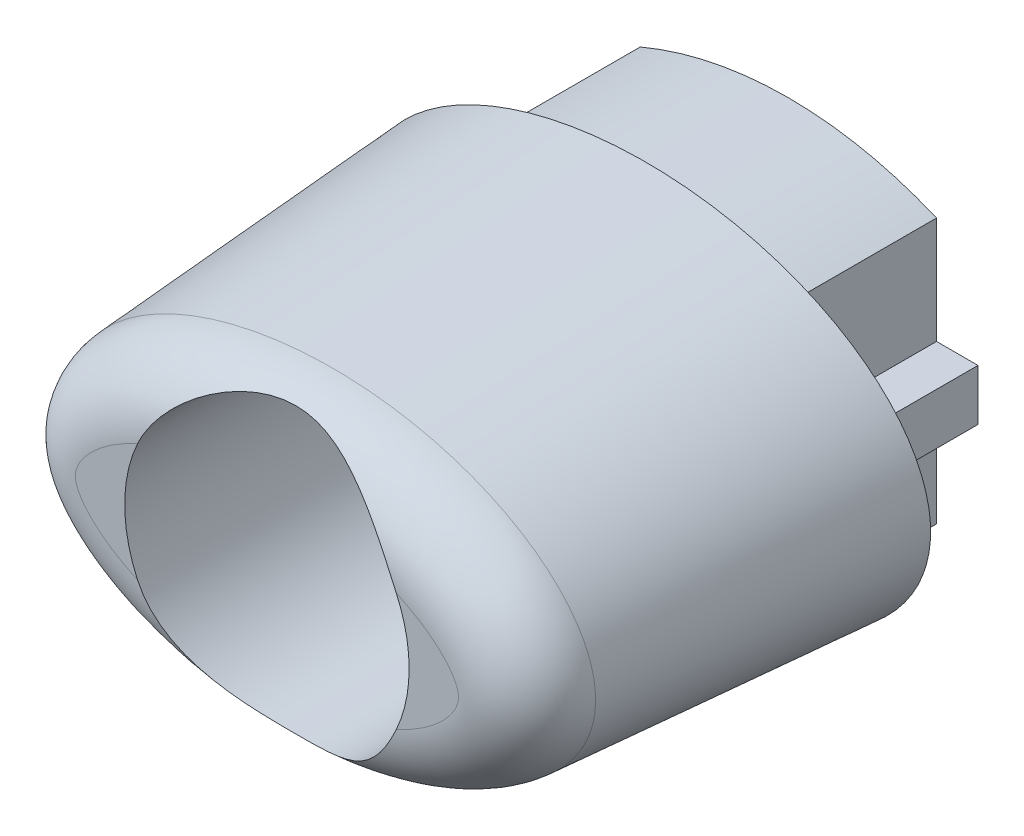
SolidWorks part; units mm, degrees
ref_plane "Front Plane" through (0, 0, 0) normal (0, 0, 1) x (1, 0, 0)
ref_plane "Top Plane" through (0, 0, 0) normal (0, 1, 0) x (1, 0, 0)
ref_plane "Right Plane" through (0, 0, 0) normal (1, 0, 0) x (0, 0, -1)
sketch "Sketch1" plane through (0, 0, 0) normal (0, 0, 1) x (1, 0, 0)
  line L0 (0, -4.2377) -> (0, 4.8119) construction
  line L1 (-6.9182, 0) -> (6.9553, 0) construction
  line L2 (-3.125, -2.7947) -> (-3.125, -0.5398)
  line L30 (-3.125, 0.5398) -> (-3.125, 2.7947)
  line L35 (3.125, 0.5398) -> (3.125, 2.7947)
  line L36 (-4, 0.5398) -> (-3.125, 0.5398)
  line L37 (4, -0.5398) -> (3.125, -0.5398)
  line L38 (4, -0.5398) -> (4, 0.5398)
  line L39 (4, 0.5398) -> (3.125, 0.5398)
  line L42 (-4, -0.5398) -> (-3.125, -0.5398)
  line L43 (-4, -0.5398) -> (-4, 0.5398)
  line L44 (3.125, -0.5398) -> (3.125, -2.7947)
  arc A2 (-3.125, 2.7947) -> (3.125, 2.7947) centre (0, -4.5731) cw
  arc A3 (-3.125, -2.7947) -> (3.125, -2.7947) centre (0, 4.5731) ccw
  ellipse E2 centre (0, 0) end of major axis (-5.39, 0) minor radius 3.43 construction
  dimension "D1" = 8
  dimension "D2" = 6.25
extrude "Boss-Extrude1" add sketch "Sketch1" along normal blind 3
sketch "Sketch3" plane through (0, 0, 3) normal (0, 0, 1) x (1, 0, 0)
  line L0 (0, 3.75) -> (0, -3.75) construction
  line L1 (-6, 0) -> (6, 0) construction
  ellipse E0 centre (0, 0) end of major axis (-6, 0) minor radius 3.75
  dimension "D1" = 7.5
  dimension "D2" = 12
extrude "Boss-Extrude2" add sketch "Sketch3" along normal blind 8 draft 4
sketch "Sketch7" plane through (0, 0, 11) normal (0, 0, 1) x (1, 0, 0)
  circle A0 centre (0, 0) radius 3
  dimension "D1" = 6
extrude "Cut-Extrude2" cut sketch "Sketch7" against normal blind 9
sketch "Sketch8" plane through (0, 0, 2) normal (0, 0, 1) x (1, 0, 0)
  line L0 (0, 3) -> (0, -3) construction
  line L1 (-4, 0) -> (4, 0) construction
  circle A0 centre (0, 0) radius 3 construction
  circle A2 centre (-1.5, 0) radius 0.25
  circle A3 centre (1.5, 0) radius 0.25
  dimension "D1" = 0.5
  dimension "D2" = 0.5
  dimension "D3" = 1.5
extrude "Cut-Extrude3" cut sketch "Sketch8" against normal blind 22
fillet "Fillet1" radius 1.5 1 edges at (-5.4061, -0.3509, 11)
